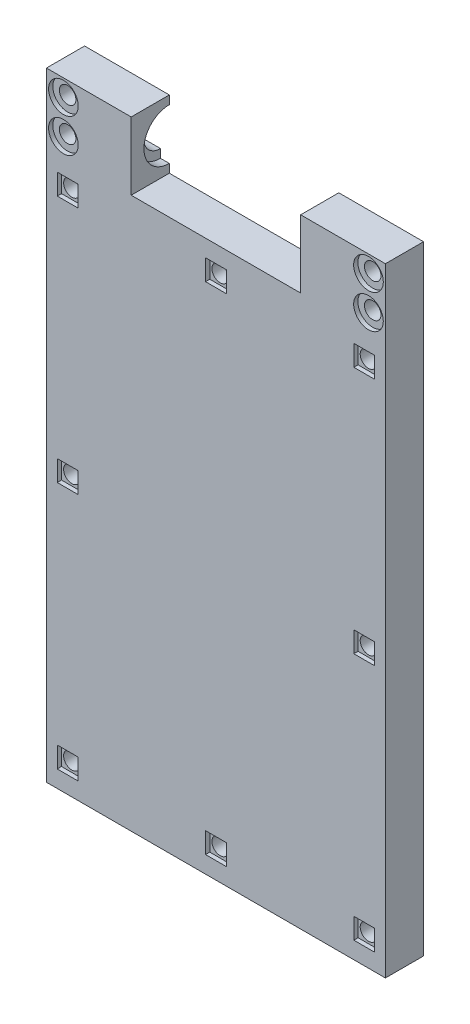
SolidWorks part; units mm, degrees
ref_plane "Ön Düzlem" through (0, 0, 0) normal (0, 0, 1) x (1, 0, 0)
ref_plane "Üst Düzlem" through (0, 0, 0) normal (0, 1, 0) x (1, 0, 0)
ref_plane "Sağ Düzlem" through (0, 0, 0) normal (1, 0, 0) x (0, 0, -1)
sketch "Çizim1" plane through (0, 0, 0) normal (0, 0, 1) x (1, 0, 0)
  line L1 (-48.9717, 83.1678) -> (-28.9717, 83.1678)
  line L2 (-48.9717, 83.1678) -> (-48.9717, -46.8322)
  line L3 (-48.9717, -46.8322) -> (31.0283, -46.8322)
  line L4 (31.0283, 83.1678) -> (31.0283, -46.8322)
  line L8 (31.0283, 83.1678) -> (31.0283, 99.1678)
  line L9 (27.0283, 79.1678) -> (27.0283, -42.8322)
  line L10 (31.0283, 99.1678) -> (11.0283, 99.1678)
  line L11 (11.0283, 99.1678) -> (11.0283, 83.1678)
  line L12 (-48.9717, 83.1678) -> (-48.9717, 99.1678)
  line L13 (-48.9717, 99.1678) -> (-28.9717, 99.1678)
  line L14 (-28.9717, 99.1678) -> (-28.9717, 83.1678)
  line L15 (-44.9717, -42.8322) -> (27.0283, -42.8322)
  line L16 (-44.9717, 79.1678) -> (-44.9717, -42.8322)
  line L17 (-44.9717, 79.1678) -> (27.0283, 79.1678)
  line L18 (11.0283, 83.1678) -> (31.0283, 83.1678)
  line L19 (-48.9717, 83.1678) -> (31.0283, 83.1678) construction
  line L20 (11.0283, 83.1678) -> (-28.9717, 83.1678)
  line L21 (11.0283, 86.1678) -> (28.0283, 86.1678)
  line L22 (28.0283, 86.1678) -> (28.0283, 96.1678)
  line L23 (28.0283, 96.1678) -> (11.0283, 96.1678)
  line L24 (-45.9717, 86.1678) -> (-28.9717, 86.1678)
  line L25 (-45.9717, 86.1678) -> (-45.9717, 96.1678)
  line L26 (-45.9717, 96.1678) -> (-28.9717, 96.1678)
extrude "Yükseklik-Ekstrüzyon3" add sketch "Çizim1" against normal blind 9 contours L23 L22 L21 L11 L18 L8 L10 | L22 L23 L11 L21 | L25 L26 L14 L13 L12 L1 L24 | L26 L25 L24 L14 region at (-48.7155, 91.1678, 0) region at (-37.4717, 91.1678, 0) region at (11.2845, 84.6678, 0) region at (19.5283, 91.1678, 0)
extrude "Yükseklik-Ekstrüzyon4" add sketch "Çizim1<4>" against normal blind 3 separate body contours L17 L16 L15 L9 region at (-8.9717, 18.1678, 0)
sketch "Çizim1<4>" plane through (0, 0, 0) normal (0, 0, 1) x (1, 0, 0) same geometry as "Çizim1"
extrude "Yükseklik-Ekstrüzyon5" add sketch "Çizim1<5>" against normal blind 9 contours L18 L20 L1 L2 L3 L4 L16 L17 L9 L15 region at (-38.9717, 81.6414, 0)
sketch "Çizim1<5>" plane through (0, 0, 0) normal (0, 0, 1) x (1, 0, 0) same geometry as "Çizim1"
sketch "Çizim2" plane through (-28.9717, 0, 0) normal (1, 0, 0) x (0, 0, -1)
  line L3 (9, 97.1678) -> (9, 85.1678)
  arc A0 (9, 95.1678) -> (9, 87.1678) centre (9, 91.1678) ccw
  arc A2 (9, 97.1678) -> (9, 85.1678) centre (9, 91.1678) ccw
extrude "Kes-Ekstrüzyon5" cut sketch "Çizim2" against normal blind 12 and the other way blind 52 contours L3 A0 region at (-28.9717, 91.1678, -7.3023)
extrude "Kes-Ekstrüzyon6" cut sketch "Çizim2<3>" against normal blind 2.08 and the other way blind 42.08 contours A2 A0 region at (-28.9717, 96.1678, -8.8658)
sketch "Çizim2<3>" plane through (-28.9717, 0, 0) normal (1, 0, 0) x (0, 0, -1) same geometry as "Çizim2"
sketch "Çizim8" plane through (0, 0, -9) normal (0, 0, -1) x (-1, 0, 0)
  line L0 (-29.5283, 81.6678) -> (-29.5283, -45.3322)
  line L5 (-29.5283, -45.3322) -> (47.4717, -45.3322)
  line L6 (47.4717, 81.6678) -> (47.4717, -45.3322)
  line L7 (-29.5283, 81.6678) -> (47.4717, 81.6678)
  line L8 (-28.5283, 80.6678) -> (-28.5283, -44.3322)
  line L9 (-28.5283, -44.3322) -> (46.4717, -44.3322)
  line L10 (46.4717, 80.6678) -> (46.4717, -44.3322)
  line L11 (-28.5283, 80.6678) -> (46.4717, 80.6678)
extrude "Kes-Ekstrüzyon9" cut sketch "Çizim8" against normal blind 1
sketch "Çizim9" plane through (0, 79.1678, 0) normal (0, -1, 0) x (1, 0, 0)
  line L1 (-34.4717, -3) -> (-34.4717, -7.5)
  line L6 (-44.9717, -3) -> (27.0283, -3) construction
  line L12 (-40.9717, -7.5) -> (-40.9717, -3)
  line L13 (-40.9717, -3) -> (-34.4717, -3)
  line L14 (-34.4717, -7.5) -> (-40.9717, -7.5)
  line L15 (16.5283, -7.5) -> (23.0283, -7.5)
  line L16 (16.5283, -3) -> (16.5283, -7.5)
  line L17 (23.0283, -3) -> (16.5283, -3)
  line L18 (23.0283, -7.5) -> (23.0283, -3)
extrude "Kes-Ekstrüzyon14" cut sketch "Çizim9" against normal blind 10
sketch "somun_yuvalar" plane through (0, 0, 0) normal (0, 0, 1) x (1, 0, 0)
  line L4 (17.0283, 98.2678) -> (22.0283, 98.2678)
  line L6 (22.0283, 98.2678) -> (22.0283, 96.5678)
  line L13 (22.0283, 96.5678) -> (17.0283, 96.5678)
  line L22 (17.0283, 84.0678) -> (22.0283, 84.0678)
  line L23 (22.0283, 84.0678) -> (22.0283, 85.7678)
  line L24 (22.0283, 85.7678) -> (17.0283, 85.7678)
  line L26 (17.0283, 98.2678) -> (17.0283, 96.5678)
  line L27 (17.0283, 85.7678) -> (17.0283, 84.0678)
  line L29 (-34.9717, 85.7678) -> (-34.9717, 84.0678)
  line L30 (-34.9717, 98.2678) -> (-34.9717, 96.5678)
  line L31 (-39.9717, 85.7678) -> (-34.9717, 85.7678)
  line L32 (-39.9717, 84.0678) -> (-39.9717, 85.7678)
  line L33 (-34.9717, 84.0678) -> (-39.9717, 84.0678)
  line L34 (-39.9717, 96.5678) -> (-34.9717, 96.5678)
  line L35 (-39.9717, 98.2678) -> (-39.9717, 96.5678)
  line L36 (-34.9717, 98.2678) -> (-39.9717, 98.2678)
  line L39 (-11.4217, 79.1678) -> (-11.4217, 74.2678)
  line L40 (-11.4217, 74.2678) -> (-6.5217, 74.2678)
  line L41 (-6.5217, 74.2678) -> (-6.5217, 79.1678)
  line L42 (-6.5217, 79.1678) -> (-11.4217, 79.1678)
  line L43 (23.5783, 79.1678) -> (23.5783, 74.2678)
  line L44 (23.5783, 74.2678) -> (28.4783, 74.2678)
  line L45 (28.4783, 74.2678) -> (28.4783, 79.1678)
  line L46 (28.4783, 79.1678) -> (23.5783, 79.1678)
  line L47 (-11.4217, 79.1678) -> (-11.4217, 74.2678)
  line L48 (-11.4217, 74.2678) -> (-6.5217, 74.2678)
  line L49 (-6.5217, 74.2678) -> (-6.5217, 79.1678)
  line L50 (-6.5217, 79.1678) -> (-11.4217, 79.1678)
  line L51 (-46.4217, 79.1678) -> (-46.4217, 74.2678)
  line L52 (-46.4217, 74.2678) -> (-41.5217, 74.2678)
  line L53 (-41.5217, 74.2678) -> (-41.5217, 79.1678)
  line L54 (-41.5217, 79.1678) -> (-46.4217, 79.1678)
  line L55 (-6.5217, -37.9322) -> (-11.4217, -37.9322)
  line L56 (28.4783, -37.9322) -> (23.5783, -37.9322)
  line L57 (-11.4217, -42.8322) -> (-6.5217, -42.8322)
  line L58 (-11.4217, -37.9322) -> (-11.4217, -42.8322)
  line L59 (-46.4217, -37.9322) -> (-46.4217, -42.8322)
  line L60 (-11.4217, -37.9322) -> (-11.4217, -42.8322)
  line L61 (-6.5217, -42.8322) -> (-6.5217, -37.9322)
  line L62 (-41.5217, -42.8322) -> (-41.5217, -37.9322)
  line L63 (-11.4217, -42.8322) -> (-6.5217, -42.8322)
  line L64 (23.5783, -42.8322) -> (28.4783, -42.8322)
  line L65 (-6.5217, -42.8322) -> (-6.5217, -37.9322)
  line L66 (23.5783, -37.9322) -> (23.5783, -42.8322)
  line L67 (-6.5217, -37.9322) -> (-11.4217, -37.9322)
  line L68 (28.4783, -42.8322) -> (28.4783, -37.9322)
  line L69 (-46.4217, -42.8322) -> (-41.5217, -42.8322)
  line L70 (-41.5217, -37.9322) -> (-46.4217, -37.9322)
  line L71 (-46.4217, 15.7178) -> (-41.5217, 15.7178)
  line L72 (-41.5217, 20.6178) -> (-46.4217, 20.6178)
  line L73 (23.5783, 15.7178) -> (28.4783, 15.7178)
  line L74 (-46.4217, 20.6178) -> (-46.4217, 15.7178)
  line L75 (28.4783, 15.7178) -> (28.4783, 20.6178)
  line L76 (-41.5217, 15.7178) -> (-41.5217, 20.6178)
  line L77 (28.4783, 20.6178) -> (23.5783, 20.6178)
  line L78 (23.5783, 20.6178) -> (23.5783, 15.7178)
  circle A0 centre (27.0283, 95.1678) radius 1.95
  circle A1 centre (27.0283, 87.1678) radius 1.95
  circle A2 centre (27.0283, 95.1678) radius 3.5
  circle A3 centre (27.0283, 87.1678) radius 3.5
  circle A4 centre (-44.9717, 87.1678) radius 3.5
  circle A5 centre (-44.9717, 95.1678) radius 3.5
  circle A6 centre (-44.9717, 87.1678) radius 1.95
  circle A7 centre (-44.9717, 95.1678) radius 1.95
  circle A9 centre (-8.9717, 76.7178) radius 1.95
  circle A10 centre (-8.9717, 76.7178) radius 1
  circle A11 centre (-44.9717, 87.1678) radius 1
  circle A12 centre (-44.9717, 95.1678) radius 1
  circle A13 centre (27.0283, 95.1678) radius 1
  circle A14 centre (27.0283, 87.1678) radius 1
  circle A15 centre (26.0283, 76.7178) radius 1.95
  circle A16 centre (26.0283, 76.7178) radius 1
  circle A17 centre (-8.9717, 76.7178) radius 1.95
  circle A18 centre (-8.9717, 76.7178) radius 1
  circle A19 centre (-43.9717, 76.7178) radius 1.95
  circle A20 centre (-43.9717, 76.7178) radius 1
  circle A21 centre (-8.9717, -40.3822) radius 1
  circle A22 centre (26.0283, -40.3822) radius 1
  circle A23 centre (26.0283, -40.3822) radius 1.95
  circle A24 centre (-43.9717, -40.3822) radius 1
  circle A25 centre (-8.9717, -40.3822) radius 1.95
  circle A26 centre (-8.9717, -40.3822) radius 1.95
  circle A27 centre (-8.9717, -40.3822) radius 1
  circle A28 centre (-43.9717, -40.3822) radius 1.95
  circle A29 centre (-43.9717, 18.1678) radius 1
  circle A30 centre (26.0283, 18.1678) radius 1
  circle A31 centre (-43.9717, 18.1678) radius 1.95
  circle A32 centre (26.0283, 18.1678) radius 1.95
  dimension "D1" = 2
  dimension "D2" = 2
sketch "centik_eklem" plane through (0, 0, -9) normal (0, 0, -1) x (-1, 0, 0)
  line L1 (-22.0283, 98.2678) -> (-17.0283, 98.2678)
  line L2 (-22.0283, 98.2678) -> (-22.0283, 96.5678)
  line L3 (-22.0283, 96.5678) -> (-17.0283, 96.5678)
  line L4 (-17.0283, 98.2678) -> (-17.0283, 96.5678)
  line L5 (-22.0283, 85.7678) -> (-17.0283, 85.7678)
  line L6 (-22.0283, 85.7678) -> (-22.0283, 84.0678)
  line L7 (-22.0283, 84.0678) -> (-17.0283, 84.0678)
  line L8 (-17.0283, 85.7678) -> (-17.0283, 84.0678)
  line L9 (34.9717, 85.7678) -> (39.9717, 85.7678)
  line L10 (34.9717, 85.7678) -> (34.9717, 84.0678)
  line L11 (34.9717, 84.0678) -> (39.9717, 84.0678)
  line L12 (39.9717, 85.7678) -> (39.9717, 84.0678)
  line L13 (34.9717, 98.2678) -> (39.9717, 98.2678)
  line L14 (34.9717, 98.2678) -> (34.9717, 96.5678)
  line L15 (34.9717, 96.5678) -> (39.9717, 96.5678)
  line L16 (39.9717, 98.2678) -> (39.9717, 96.5678)
extrude "Kes-Ekstrüzyon15" cut sketch "centik_eklem" against normal blind 6
sketch "Çizim17" plane through (0, 0, -3) normal (0, 0, -1) x (-1, 0, 0)
  line L0 (-27.0283, 79.1678) -> (-27.0283, -42.8322)
  line L1 (-27.0283, 79.1678) -> (-27.0283, -42.8322) construction
  line L2 (44.9717, -42.8322) -> (-27.0283, -42.8322) construction
  line L3 (-27.0283, -42.8322) -> (44.9717, -42.8322)
  line L4 (44.9717, -42.8322) -> (44.9717, 79.1678)
  line L5 (44.9717, 79.1678) -> (-27.0283, 79.1678)
  line L6 (-27.0283, -42.8322) -> (-23.5783, -42.8322)
  line L7 (-23.5783, -42.8322) -> (-23.5783, -37.9322)
  line L8 (-23.5783, -37.9322) -> (-27.0283, -37.9322)
  line L9 (-28.4783, -37.9322) -> (-23.5783, -37.9322) construction
  line L10 (-27.0283, -37.9322) -> (-27.0283, -42.8322)
  line L11 (6.5217, -42.8322) -> (6.5217, -37.9322)
  line L12 (6.5217, -37.9322) -> (11.4217, -37.9322)
  line L13 (11.4217, -37.9322) -> (11.4217, -42.8322)
  line L14 (11.4217, -42.8322) -> (6.5217, -42.8322)
  line L15 (41.5217, -37.9322) -> (44.9717, -37.9322)
  line L16 (41.5217, -37.9322) -> (46.4217, -37.9322) construction
  line L17 (44.9717, -37.9322) -> (44.9717, -42.8322)
  line L18 (41.5217, -37.9322) -> (41.5217, -42.8322)
  line L19 (41.5217, -42.8322) -> (44.9717, -42.8322)
  line L20 (41.5217, 20.6178) -> (44.9717, 20.6178)
  line L21 (41.5217, 20.6178) -> (46.4217, 20.6178) construction
  line L22 (44.9717, 20.6178) -> (44.9717, 15.6862)
  line L23 (44.9717, 15.6862) -> (41.5217, 15.7178)
  line L24 (41.5217, 15.7178) -> (41.5217, 20.6178)
  line L25 (44.9717, 79.1678) -> (41.5217, 79.1678)
  line L26 (41.5217, 79.1678) -> (41.5217, 74.2678)
  line L27 (41.5217, 74.2678) -> (44.9717, 74.2678)
  line L28 (46.4217, 74.2678) -> (41.5217, 74.2678) construction
  line L29 (44.9717, 74.2678) -> (44.9717, 79.1678)
  line L30 (6.5217, 79.1678) -> (6.5217, 74.2678)
  line L31 (6.5217, 74.2678) -> (11.4217, 74.2678)
  line L32 (11.4217, 74.2678) -> (11.4217, 79.1678)
  line L33 (11.4217, 79.1678) -> (6.5217, 79.1678)
  line L34 (-23.5783, 79.1678) -> (-23.5783, 74.2678)
  line L35 (-23.5783, 74.2678) -> (-27.0283, 74.2678)
  line L36 (-27.0283, 74.2678) -> (-27.0283, 79.1678)
  line L37 (-27.0283, 79.1678) -> (-23.5783, 79.1678)
  line L38 (-23.5783, 20.6178) -> (-23.5783, 15.7178)
  line L39 (-23.5783, 15.7178) -> (-27.0283, 15.7178)
  line L40 (-23.5783, 15.7178) -> (-28.4783, 15.7178) construction
  line L41 (-27.0283, 15.7178) -> (-27.0283, 20.6178)
  line L42 (-28.4783, 20.6178) -> (-23.5783, 20.6178) construction
  line L43 (-27.0283, 20.6178) -> (-23.5783, 20.6178)
  line M5 (44.9717, 79.1678) -> (40.9717, 79.1678)
  line M14 (-27.0283, 79.1678) -> (-27.0283, -42.8322)
  line M15 (-27.0283, -42.8322) -> (44.9717, -42.8322)
  line M16 (44.9717, -42.8322) -> (44.9717, 79.1678)
extrude "Yükseklik-Ekstrüzyon6" add sketch "Çizim17" along normal blind 6 contours L43 L39 L38 M14 | L35 L34 L5 M14 | L31 L32 L5 L30 | L13 L12 L11 M15 | L7 L8 L0 M15 | L15 L18 M15 M16 | L24 L23 L20 M16 | L26 L27 L4 M5 region at (25.3033, 76.7178, -3) region at (25.3033, 18.1678, -3) region at (-8.9717, 76.7178, -3) region at (25.3033, -40.3822, -3) region at (-43.2467, 76.7178, -3) region at (-8.9717, -40.3822, -3) region at (-43.2485, 18.1599, -3) region at (-43.2467, -40.3822, -3)
extrude "Kes-Ekstrüzyon16" cut sketch "somun_yuvalar" against normal blind 9 contours A30 | A29 | A24 | A21 | A22 | A16 | A10 | A20 | A12 | A11 | A14 | A13 region at (-8.9717, 76.7178, 0) region at (-44.9717, 87.1678, 0) region at (-44.9717, 95.1678, 0) region at (27.0283, 95.1678, 0) region at (27.0283, 87.1678, 0) region at (26.0283, 76.7178, 0) region at (-43.9717, 76.7178, 0) region at (-8.9717, -40.3822, 0) region at (26.0283, -40.3822, 0) region at (-43.9717, -40.3822, 0) region at (-43.9717, 18.1678, 0) region at (26.0283, 18.1678, 0)
extrude "Kes-Ekstrüzyon17" cut sketch "somun_yuvalar<3>" against normal blind 4 contours A19 A20 | A9 A10 | A15 A16 | A32 A30 | A23 A22 | A25 A21 | A28 A24 | A31 A29 | A6 A11 | A7 A12 | A0 A13 | A1 A14 region at (25.1335, 95.1678, 0) region at (25.1335, 87.1678, 0) region at (-46.8665, 87.1678, 0) region at (-46.8665, 95.1678, 0) region at (-10.8665, 76.7178, 0) region at (24.1335, 76.7178, 0) region at (-45.8665, 76.7178, 0) region at (24.1335, -40.3822, 0) region at (-10.8665, -40.3822, 0) region at (-45.8665, -40.3822, 0) region at (-45.8665, 18.1678, 0) region at (24.1335, 18.1678, 0)
sketch "somun_yuvalar<3>" plane through (0, 0, 0) normal (0, 0, 1) x (1, 0, 0) same geometry as "somun_yuvalar"
extrude "Kes-Ekstrüzyon18" cut sketch "somun_yuvalar<4>" against normal blind 1 contours L53 L54 L51 L52 A19 | L41 L42 L39 L40 A9 | L45 L46 L43 L44 A15 | L77 L78 L73 L75 A32 | L64 L68 L56 L66 A23 | L57 L61 L55 L58 A25 | L62 L70 L59 L69 A28 | L71 L76 L72 L74 A31 | A4 | A5 | A2 | A3 region at (-8.9717, 79.0985, 0) region at (26.0283, 79.0985, 0) region at (-43.9717, 79.0985, 0) region at (-6.591, -40.3822, 0) region at (28.409, -40.3822, 0) region at (-43.9717, -38.0015, 0) region at (-46.3524, 18.1678, 0) region at (23.6476, 18.1678, 0)
sketch "somun_yuvalar<4>" plane through (0, 0, 0) normal (0, 0, 1) x (1, 0, 0) same geometry as "somun_yuvalar"
sketch "Çizim18" plane through (0, 0, -3) normal (0, 0, -1) x (-1, 0, 0)
  line L0 (-11.0283, 99.1678) -> (-31.0283, 99.1678)
  line L1 (-31.0283, 99.1678) -> (-31.0283, 83.1678)
  line L2 (-31.0283, -46.8322) -> (-31.0283, 99.1678) construction
  line L5 (28.9717, 99.1678) -> (28.9717, 83.1678)
  line L7 (48.9717, 99.1678) -> (48.9717, -46.8322) construction
  line L8 (48.9717, 83.1678) -> (48.9717, 99.1678)
  line L9 (48.9717, 99.1678) -> (28.9717, 99.1678)
  line L10 (-31.0283, 83.1678) -> (48.9717, 83.1678)
  line L11 (-31.0283, 83.1678) -> (-31.0283, -46.8322)
  line L12 (-31.0283, -46.8322) -> (48.9717, -46.8322)
  line L13 (48.9717, -46.8322) -> (48.9717, 83.1678)
  line L14 (-11.0283, 99.1678) -> (-11.0283, 83.1678)
  line L15 (-29.4283, 81.5678) -> (-29.4283, -45.2322)
  line L16 (-29.4283, -45.2322) -> (47.3717, -45.2322)
  line L17 (47.3717, -45.2322) -> (47.3717, 81.5678)
  line L18 (-29.4283, 81.5678) -> (47.3717, 81.5678)
  line L19 (-29.4283, 83.1678) -> (-29.4283, -45.2322) construction
  line L20 (-31.0283, 81.5678) -> (48.9717, 81.5678) construction
  line L21 (47.3717, -45.2322) -> (47.3717, 83.1678) construction
  line L22 (-28.6283, 80.7678) -> (46.5717, 80.7678)
  line L23 (46.5717, -44.4322) -> (46.5717, 80.7678)
  line L24 (-28.6283, -44.4322) -> (46.5717, -44.4322)
  line L25 (-28.6283, 80.7678) -> (-28.6283, -44.4322)
  line L26 (-23.5783, 74.2678) -> (-23.5783, 79.1678)
  line L27 (-23.5783, 79.1678) -> (6.5217, 79.1678)
  line L28 (6.5217, 79.1678) -> (6.5217, 74.2678)
  line L29 (6.5217, 74.2678) -> (11.4217, 74.2678)
  line L30 (11.4217, 74.2678) -> (11.4217, 79.1678)
  line L31 (11.4217, 79.1678) -> (41.5217, 79.1678)
  line L32 (41.5217, 79.1678) -> (41.5217, 74.2678)
  line L33 (41.5217, 74.2678) -> (44.9717, 74.2678)
  line L34 (44.9717, 74.2678) -> (44.9717, 20.6178)
  line L35 (44.9717, 20.6178) -> (41.5217, 20.6178)
  line L36 (41.5217, 20.6178) -> (41.5217, 15.7178)
  line L37 (41.5217, 15.7178) -> (44.9717, 15.6862)
  line L38 (44.9717, 15.6862) -> (44.9717, -37.9322)
  line L39 (44.9717, -37.9322) -> (41.5217, -37.9322)
  line L40 (41.5217, -37.9322) -> (41.5217, -42.8322)
  line L41 (41.5217, -42.8322) -> (11.4217, -42.8322)
  line L42 (11.4217, -42.8322) -> (11.4217, -37.9322)
  line L43 (11.4217, -37.9322) -> (6.5217, -37.9322)
  line L44 (6.5217, -37.9322) -> (6.5217, -42.8322)
  line L45 (6.5217, -42.8322) -> (-23.5783, -42.8322)
  line L46 (-23.5783, -42.8322) -> (-23.5783, -37.9322)
  line L47 (-23.5783, -37.9322) -> (-27.0283, -37.9322)
  line L48 (-27.0283, -37.9322) -> (-27.0283, 15.7178)
  line L49 (-27.0283, 15.7178) -> (-23.5783, 15.7178)
  line L50 (-23.5783, 15.7178) -> (-23.5783, 20.6178)
  line L51 (-23.5783, 20.6178) -> (-27.0283, 20.6178)
  line L52 (-27.0283, 20.6178) -> (-27.0283, 74.2678)
  line L53 (-27.0283, 74.2678) -> (-23.5783, 74.2678)
  line L54 (35.0717, 85.6678) -> (35.0717, 84.1678)
  line L71 (35.0717, 84.1678) -> (39.8717, 84.1678)
  line L72 (39.8717, 85.6678) -> (39.8717, 84.1678)
  line L73 (35.0717, 85.6678) -> (39.8717, 85.6678)
  line L74 (35.0717, 98.1678) -> (35.0717, 96.6678)
  line L75 (35.0717, 96.6678) -> (39.8717, 96.6678)
  line L76 (39.8717, 98.1678) -> (39.8717, 96.6678)
  line L77 (35.0717, 98.1678) -> (39.8717, 98.1678)
  line L78 (-21.9283, 98.1678) -> (-21.9283, 96.6678)
  line L79 (-21.9283, 96.6678) -> (-17.1283, 96.6678)
  line L80 (-17.1283, 98.1678) -> (-17.1283, 96.6678)
  line L81 (-21.9283, 98.1678) -> (-17.1283, 98.1678)
  line L82 (-21.9283, 85.6678) -> (-21.9283, 84.1678)
  line L83 (-21.9283, 84.1678) -> (-17.1283, 84.1678)
  line L84 (-17.1283, 85.6678) -> (-17.1283, 84.1678)
  line L85 (-21.9283, 85.6678) -> (-17.1283, 85.6678)
  circle A0 centre (-26.0283, 76.7178) radius 1
  circle A1 centre (-27.0283, 87.1678) radius 1
  circle A2 centre (-27.0283, 95.1678) radius 1
  circle A3 centre (44.9717, 95.1678) radius 1
  circle A4 centre (44.9717, 87.1678) radius 1
  circle A5 centre (43.9717, 76.7178) radius 1
  circle A6 centre (8.9717, 76.7178) radius 1
  circle A7 centre (43.9717, 18.1678) radius 1
  circle A8 centre (43.9717, -40.3822) radius 1
  circle A9 centre (8.9717, -40.3822) radius 1
  circle A10 centre (-26.0283, -40.3822) radius 1
  circle A11 centre (-26.0283, 18.1678) radius 1
